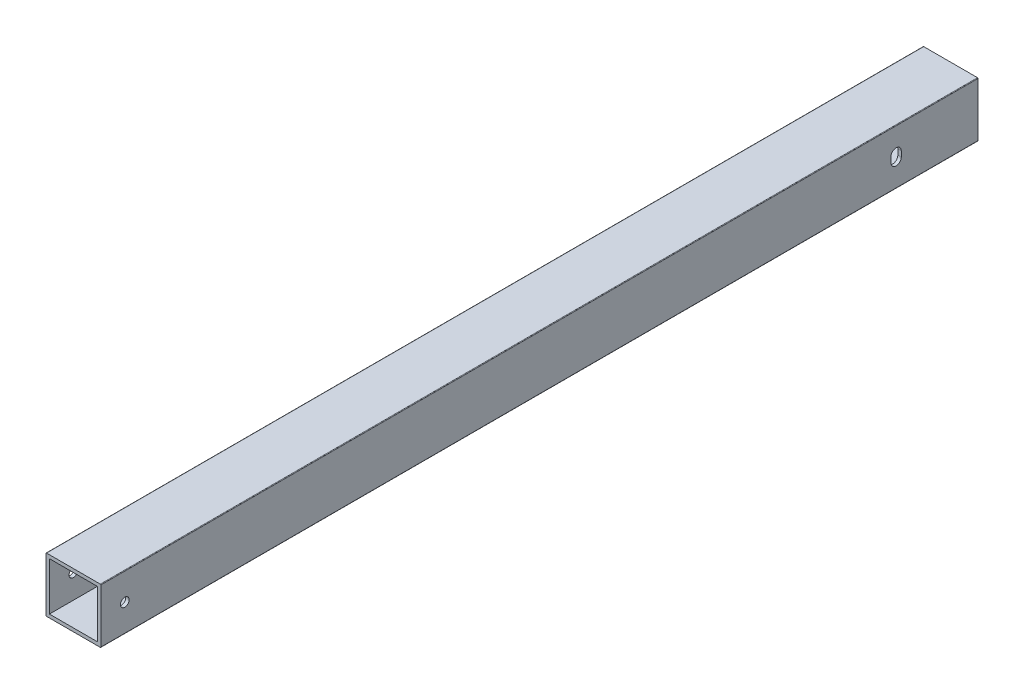
SolidWorks part; units mm, degrees
material "1060 Alloy"
ref_plane "Front Plane" through (0, 0, 0) normal (0, 0, 1) x (1, 0, 0)
ref_plane "Top Plane" through (0, 0, 0) normal (0, 1, 0) x (1, 0, 0)
ref_plane "Right Plane" through (0, 0, 0) normal (1, 0, 0) x (0, 0, -1)
ref_plane "Plane1" through (0, 0, 0) normal (0, 0, -1) x (-1, 0, 0)
sketch "Sketch1" plane through (0, 0, 0) normal (0, 0, -1) x (-1, 0, 0)
  line L4 (1.5875, -1.3335) -> (1.5875, 23.5585)
  line L5 (1.3335, 23.8125) -> (-23.5585, 23.8125)
  line L6 (-23.8125, 23.5585) -> (-23.8125, -1.3335)
  line L7 (-23.5585, -1.5875) -> (1.3335, -1.5875)
  line L9 (0, 22.225) -> (-22.225, 22.225)
  line L10 (0, 22.225) -> (0, 0)
  line L11 (0, 0) -> (-22.225, 0)
  line L12 (-22.225, 22.225) -> (-22.225, 0)
  line L13 (0, 22.225) -> (-22.225, 0) construction
  line L14 (0, 0) -> (-22.225, 22.225) construction
  arc A4 (1.3335, -1.5875) -> (1.5875, -1.3335) centre (1.3335, -1.3335) ccw
  arc A5 (1.5875, 23.5585) -> (1.3335, 23.8125) centre (1.3335, 23.5585) ccw
  arc A6 (-23.5585, 23.8125) -> (-23.8125, 23.5585) centre (-23.5585, 23.5585) ccw
  arc A7 (-23.8125, -1.3335) -> (-23.5585, -1.5875) centre (-23.5585, -1.3335) ccw
  point P24 (-11.1125, 11.1125)
  dimension "D1" = 25.4
  dimension "D2" = 25.4
  dimension "D3" = 1.5875
  dimension "D4" = 1.5875
  dimension "D5" = 1.5875
extrude "Boss-Extrude1" add sketch "Sketch1" against normal blind 406.4
sketch "Sketch2" plane through (-1.5875, 0, 0) normal (-1, 0, 0) x (0, 0, 1)
  line L0 (0, -1.3335) -> (0, 23.5585) construction
  line L1 (406.4, -1.3335) -> (0, -1.3335) construction
  line L2 (406.4, -1.3335) -> (406.4, 23.5585) construction
  circle A0 centre (12.6975, 11.3665) radius 1.5875
  circle A1 centre (393.7, 11.3665) radius 1.5875
  circle A2 centre (76.2, 11.3665) radius 6.35
  circle A3 centre (330.2, 11.3665) radius 6.35
  point P4 (0, 11.1125)
  dimension "D1" = 3.175
  dimension "D2" = 12.7
  dimension "D3" = 12.7
  dimension "D4" = 3.175
  dimension "D5" = 12.7
  dimension "D6" = 12.7
  dimension "D7" = 12.7
  dimension "D8" = 12.7
  dimension "D9" = 76.2
  dimension "D10" = 12.7
  dimension "D11" = 12.7
  dimension "D12" = 76.2
extrude "Cut-Extrude1" [suppressed] cut sketch "Sketch2" against normal through all
sketch "Sketch3" plane through (-1.5875, 0, 0) normal (-1, 0, 0) x (0, 0, 1)
  circle A0 centre (18.2509, 12.9013) radius 4.7907
sketch "Sketch4" plane through (23.8125, 0, 0) normal (1, 0, 0) x (0, 0, -1)
  line L2 (-40.3145, 9.8425) -> (-40.3145, 12.3825)
  line L4 (-35.552, 9.8425) -> (-35.552, 12.3825)
  line L6 (-40.3145, 12.3825) -> (-35.552, 12.3825)
  line L7 (-40.3145, 11.1125) -> (-35.552, 11.1125)
  line L8 (0, 23.5585) -> (0, -1.3335) construction
  line L9 (0, 11.1125) -> (-49.6378, 11.1125)
  circle A0 centre (-37.9333, 9.8425) radius 2.3812
  circle A1 centre (-37.9333, 12.3825) radius 2.3812
  dimension "D1" = 4.7625
  dimension "D2" = 37.9333
  dimension "D3" = 1.27
extrude "Cut-Extrude2" cut sketch "Sketch4" against normal through all contours L6 A1 | L6 A1 A0 | L9 A0 | L9 A1 | A1 A0 | A0 L4 L7 | A1 L7 L4 | A0 L7 L2 | A1 L2 L7 | A0 region at (23.8125, 9.1445, 37.9333) region at (23.8125, 10.8001, 40.2061) region at (23.8125, 11.4249, 40.2061) region at (23.8125, 10.8001, 35.6605) region at (23.8125, 11.5673, 37.9333) region at (23.8125, 11.7352, 40.1736) region at (23.8125, 10.6577, 37.9333) region at (23.8125, 13.3931, 37.9333) region at (23.8125, 11.4249, 35.6605)
ref_plane "Plane2" through (-1.5875, -1.3335, 406.4) normal (0, 0, -1) x (-1, 0, 0)
sketch "Sketch6" plane through (-1.5875, 0, 0) normal (-1, 0, 0) x (0, 0, 1)
  line L0 (406.4, 23.8125) -> (0, 23.8125) construction
  line L1 (406.4, 110.4265) -> (406.4, -113.0935) construction
  circle A0 centre (395.2875, 11.1125) radius 2.0193
  dimension "D1" = 4.0386
  dimension "D2" = 12.7
  dimension "D3" = 11.1125
extrude "Cut-Extrude3" cut sketch "Sketch6" against normal through all
